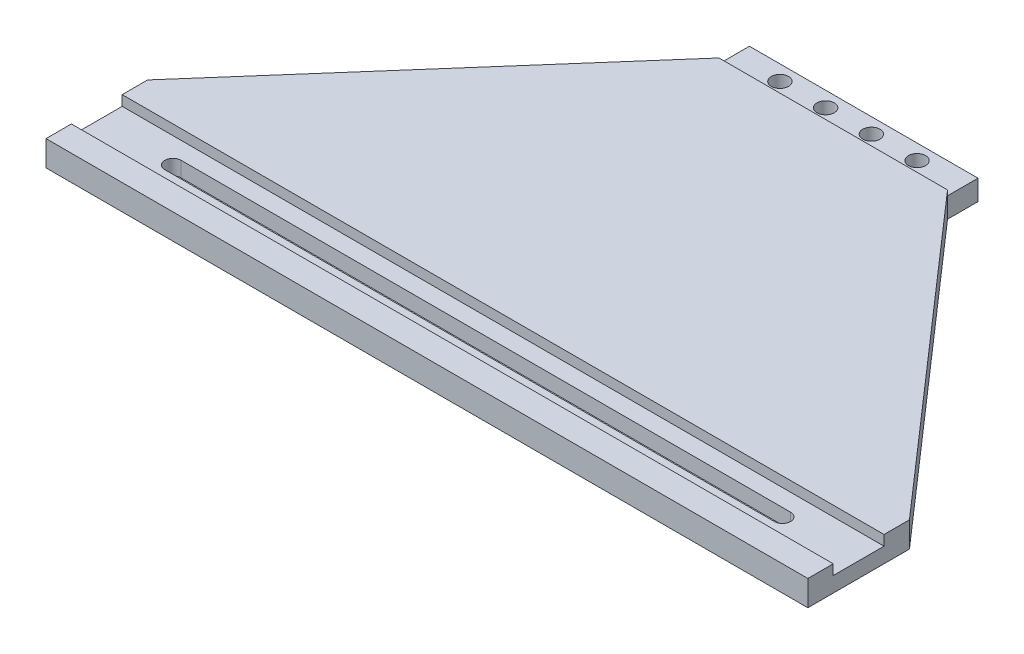
SolidWorks part; units mm, degrees
ref_plane "Спереди" through (0, 0, 0) normal (0, 0, 1) x (1, 0, 0)
ref_plane "Сверху" through (0, 0, 0) normal (0, 1, 0) x (1, 0, 0)
ref_plane "Справа" through (0, 0, 0) normal (1, 0, 0) x (0, 0, -1)
sketch "Эскиз1" plane through (0, 0, 0) normal (0, 1, 0) x (1, 0, 0)
  line L0 (-22.5, 0) -> (22.5, 0) construction
  line L1 (-22.5, 3) -> (22.5, 3)
  line L2 (-22.5, 3) -> (-22.5, -3)
  line L3 (-22.5, -3) -> (22.5, -3) construction
  line L4 (22.5, 3) -> (22.5, -3)
  line L5 (-22.5, 3) -> (22.5, -3) construction
  line L6 (-22.5, -3) -> (22.5, 3) construction
  line L7 (0, 3) -> (0, -3) construction
  line L8 (-22.5, -3) -> (-75, -63)
  line L9 (-75, -63) -> (-75, -83)
  line L10 (-75, -83) -> (75, -83)
  line L11 (75, -83) -> (75, -63)
  line L12 (75, -63) -> (22.5, -3)
  line L13 (0, -3) -> (0, -163) construction
  line L14 (75, -63) -> (-75, -63) construction
  line L15 (-13.5, 3) -> (-13.5, -3) construction
  line L16 (-4.5, 3) -> (-4.5, -3) construction
  line L17 (4.5, 3) -> (4.5, -3) construction
  line L18 (13.5, 3) -> (13.5, -3) construction
  point P0 (0, 0)
  point P10 (0, -83)
  dimension "D1" = 45
  dimension "D2" = 6
  dimension "D3" = 150
  dimension "D4" = 80
  dimension "D5" = 20
  dimension "D6" = 9
  dimension "D7" = 9
  dimension "D8" = 9
  dimension "D9" = 9
extrude "Бобышка-Вытянуть1" add sketch "Эскиз1" along normal blind 5
sketch "Эскиз2" plane through (0, 5, 0) normal (0, 1, 0) x (1, 0, 0)
  line L0 (75, -83) -> (75, -63) construction
  line L1 (-75, -78) -> (75, -78)
  line L2 (-75, -78) -> (-75, -68)
  line L3 (-75, -68) -> (75, -68)
  line L4 (75, -78) -> (75, -68)
  line L5 (-75, -83) -> (75, -83) construction
  dimension "D1" = 10
  dimension "D2" = 5
extrude "Вырез-Вытянуть1" cut sketch "Эскиз2" against normal blind 2
sketch "Эскиз3" plane through (0, 5, 0) normal (0, 1, 0) x (1, 0, 0)
  line L1 (-22.5, 3) -> (22.5, 3)
  line L2 (-22.5, 3) -> (-22.5, -3)
  line L3 (-22.5, -3) -> (22.5, -3)
  line L4 (22.5, 3) -> (22.5, -3)
extrude "Вырез-Вытянуть2" cut sketch "Эскиз3" against normal blind 1
hole_wizard "Отверстие с зазором M31" positions "Эскиз8" profile "Эскиз7" hole size "M3" standard "Ansi Metric" end condition through all
sketch "Эскиз8" plane through (0, 0, 0) normal (0, -1, 0) x (-1, 0, 0)
  line L0 (-13.5, 3) -> (-13.5, -3) construction
  line L1 (-4.5, 3) -> (-4.5, -3) construction
  line L2 (4.5, 3) -> (4.5, -3) construction
  line L3 (13.5, 3) -> (13.5, -3) construction
  point P0 (-13.5, 0)
  point P4 (-4.5, 0)
  point P8 (4.5, 0)
  point P12 (13.5, 0)
sketch "Эскиз7" plane through (13.5, 0, 0) normal (1, 0, 0) x (0, 0, -1)
  line L0 (0, 0) -> (0, 5)
  line L1 (0, 5) -> (1.7, 5)
  line L2 (1.7, 5) -> (1.7, 0)
  line L5 (1.7, 0) -> (0, 0)
  line L11 (0, -6.35) -> (0, 107.95) construction
  dimension "Диаметр сквозного отверстия" = 3.4
  dimension "Глубина сквозного отверстия" = 5
sketch "Эскиз9" plane through (0, 3, 0) normal (0, 1, 0) x (1, 0, 0)
  line L0 (-60, -73) -> (60, -73) construction
  line L1 (-60, -71.4) -> (60, -71.4)
  line L2 (-60, -74.6) -> (60, -74.6)
  line L3 (0, -68) -> (0, -78) construction
  line L4 (75, -68) -> (-75, -68) construction
  line L5 (-75, -78) -> (75, -78) construction
  arc A0 (-60, -71.4) -> (-60, -74.6) centre (-60, -73) ccw
  arc A1 (60, -74.6) -> (60, -71.4) centre (60, -73) ccw
  point P2 (0, -73)
  dimension "D1" = 1.6
  dimension "D2" = 120
extrude "Вырез-Вытянуть3" cut sketch "Эскиз9" against normal through all
equation "\"D6@Эскиз1\"=\"D1@Эскиз1\"/5"
equation "\"D7@Эскиз1\"=\"D6@Эскиз1\""
equation "\"D8@Эскиз1\"=\"D6@Эскиз1\""
equation "\"D9@Эскиз1\"=\"D6@Эскиз1\""
